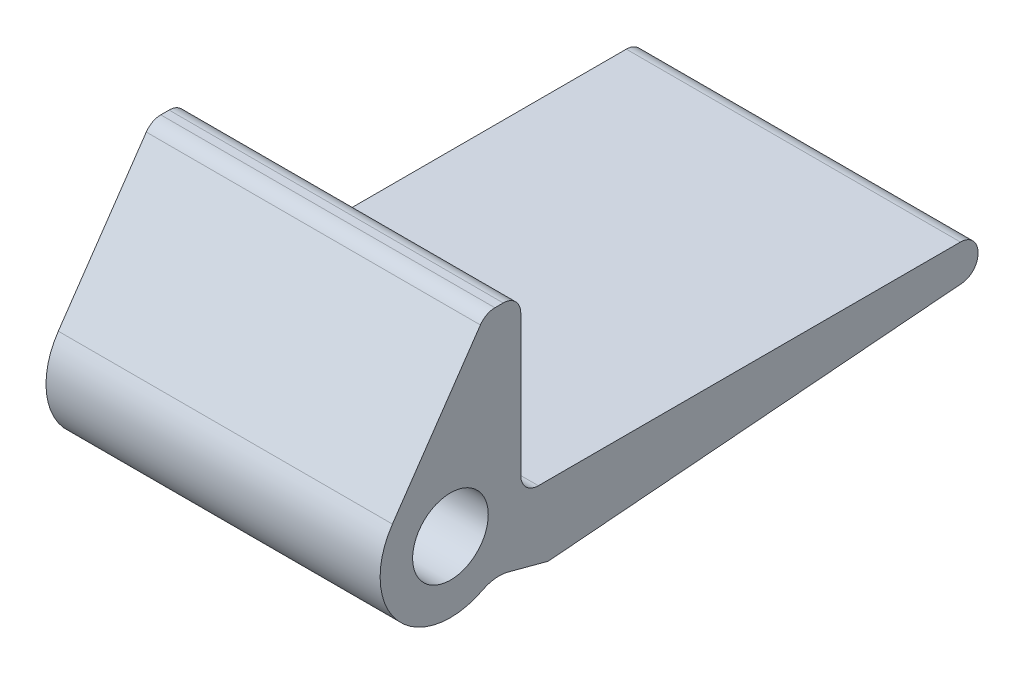
SolidWorks part; units mm, degrees
ref_plane "Front Plane" through (0, 0, 0) normal (0, 0, 1) x (1, 0, 0)
ref_plane "Top Plane" through (0, 0, 0) normal (0, 1, 0) x (1, 0, 0)
ref_plane "Right Plane" through (0, 0, 0) normal (1, 0, 0) x (0, 0, -1)
sketch "Sketch1" plane through (0, 0, 0) normal (1, 0, 0) x (0, 0, -1)
  line L5 (2.4402, -3.1695) -> (5.5539, -4)
  line L17 (4, 0) -> (30, 0)
  line L18 (30, -2) -> (30, 0)
  line L19 (2, 10) -> (4, 10)
  line L22 (4, 10) -> (4, 0)
  line L24 (2, 10) -> (-3.3003, 2.2601)
  line L25 (30, -2) -> (5.5539, -4)
  circle A5 centre (0, 0) radius 2.15
  arc A6 (-3.3003, 2.2601) -> (2.4402, -3.1695) centre (0, 0) ccw
extrude "Boss-Extrude1" add sketch "Sketch1" along normal mid plane 19
fillet "Fillet1" radius 2 1 edges at (0, -3.1695, -2.4402)
fillet "Fillet2" radius 1 3 edges at (0, 0, -30) (0, 10, -4) (0, 0, -4)
fillet "Fillet3" radius 1 2 edges at (0, -2, -30) (0, 10, -2)
